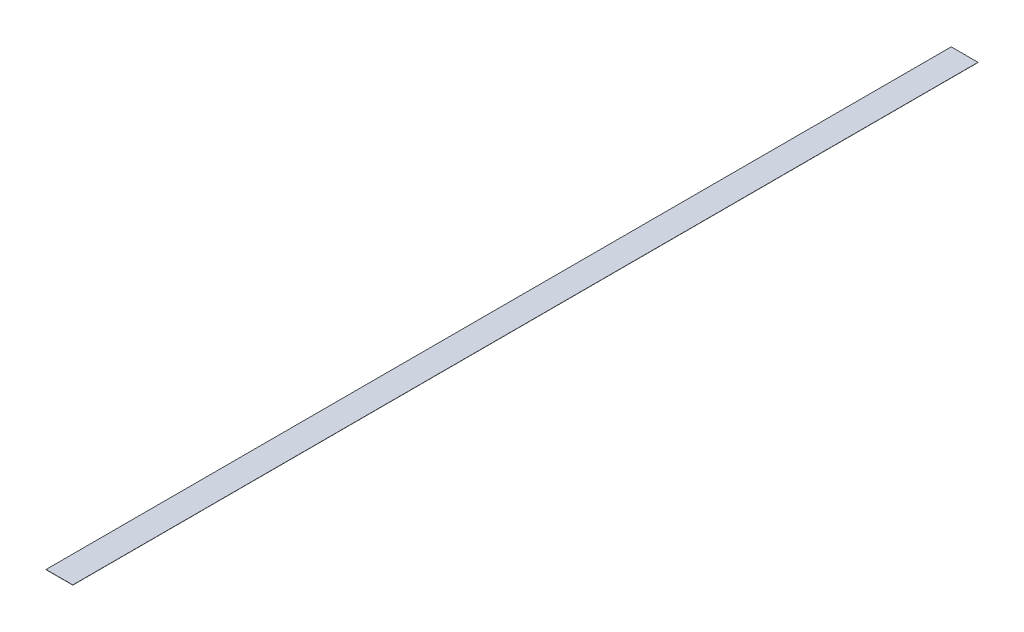
SolidWorks part; units mm, degrees
ref_plane "Front Plane" through (0, 0, 0) normal (0, 0, 1) x (1, 0, 0)
ref_plane "Top Plane" through (0, 0, 0) normal (0, 1, 0) x (1, 0, 0)
ref_plane "Right Plane" through (0, 0, 0) normal (1, 0, 0) x (0, 0, -1)
sketch "Sketch1" plane through (0, 0, 0) normal (0, 1, 0) x (1, 0, 0)
  line L5 (0, 0) -> (15, 0)
  line L6 (0, 0) -> (0, -507)
  line L7 (0, -507) -> (15, -507)
  line L8 (15, 0) -> (15, -507)
  dimension "D1" = 507
  dimension "D2" = 15
extrude "Boss-Extrude1" add sketch "Sketch1" along normal blind 0.1 contours L6 L7 L8 L5
sketch "Sketch2" plane through (0, 0.1, 0) normal (0, 1, 0) x (1, 0, 0)
  line L0 (0, -487) -> (15, -483.537) construction
  line L1 (0, 0) -> (0, -507) construction
  line L2 (15, 0) -> (15, -507) construction
  line L3 (5.0641, -485.8309) -> (5.0641, -457.2309) construction
  circle A0 centre (5.0641, -485.8309) radius 1
  circle A1 centre (9.9359, -484.7061) radius 1
  circle A2 centre (5.0641, -457.2309) radius 1
  circle A3 centre (9.9359, -456.1061) radius 1
  circle A4 centre (5.0641, -428.6309) radius 1
  circle A5 centre (9.9359, -427.5061) radius 1
  circle A6 centre (5.0641, -400.0309) radius 1
  circle A7 centre (9.9359, -398.9061) radius 1
  circle A8 centre (5.0641, -371.4309) radius 1
  circle A9 centre (9.9359, -370.3061) radius 1
  circle A10 centre (5.0641, -342.8309) radius 1
  circle A11 centre (9.9359, -341.7061) radius 1
  circle A12 centre (5.0641, -314.2309) radius 1
  circle A13 centre (9.9359, -313.1061) radius 1
  circle A14 centre (5.0641, -285.6309) radius 1
  circle A15 centre (9.9359, -284.5061) radius 1
  circle A16 centre (5.0641, -257.0309) radius 1
  circle A17 centre (9.9359, -255.9061) radius 1
  circle A18 centre (5.0641, -228.4309) radius 1
  circle A19 centre (9.9359, -227.3061) radius 1
  circle A20 centre (5.0641, -199.8309) radius 1
  circle A21 centre (9.9359, -198.7061) radius 1
  circle A22 centre (5.0641, -171.2309) radius 1
  circle A23 centre (9.9359, -170.1061) radius 1
  circle A24 centre (5.0641, -142.6309) radius 1
  circle A25 centre (9.9359, -141.5061) radius 1
  circle A26 centre (5.0641, -114.0309) radius 1
  circle A27 centre (9.9359, -112.9061) radius 1
  circle A28 centre (5.0641, -85.4309) radius 1
  circle A29 centre (9.9359, -84.3061) radius 1
  circle A30 centre (5.0641, -56.8309) radius 1
  circle A31 centre (9.9359, -55.7061) radius 1
  point P13 (7.5, -485.2685)
  dimension "D3" = 2
  dimension "D4" = 5
  dimension "D1" = 20
  dimension "D2" = 77
  dimension "D5" = 2.5
  dimension "D7" = 28.6
  dimension "D6" = 16
extrude "Cut-Extrude1" [suppressed] cut sketch "Sketch2" against normal through all
ref_plane "Plane1" through (7.5, 0, 0) normal (1, 0, 0) x (0, 0, -1)
